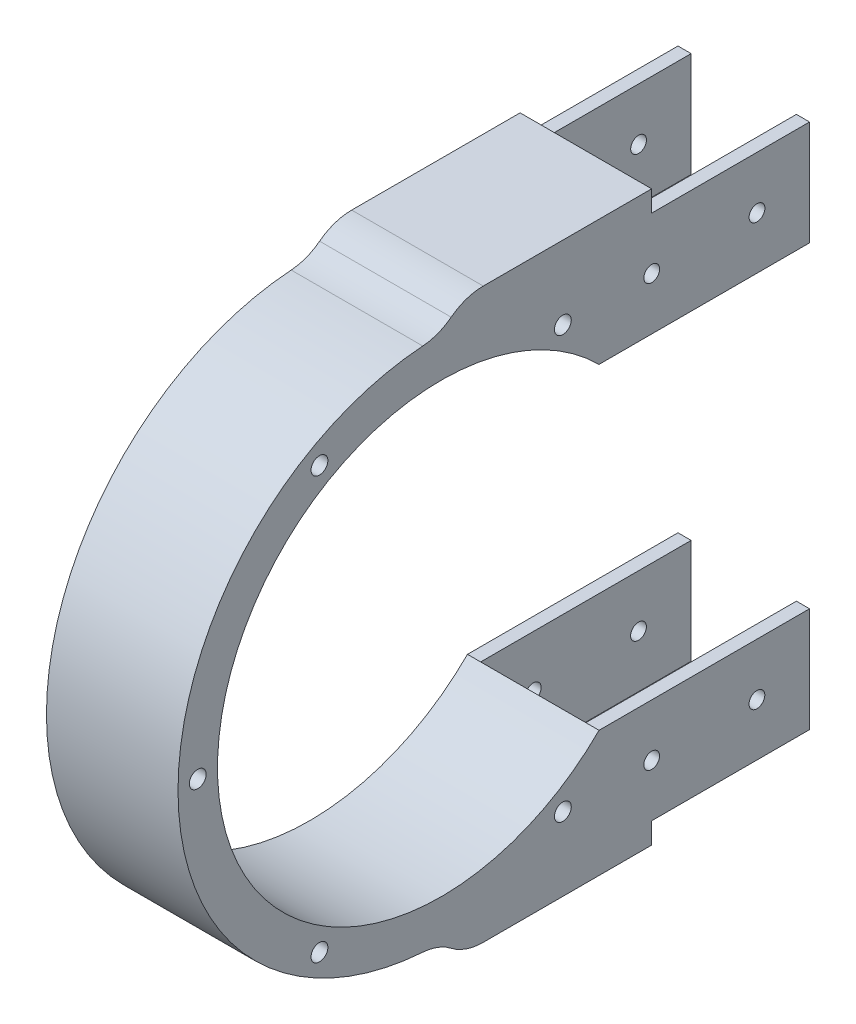
SolidWorks part; units mm, degrees
ref_plane "Front Plane" through (0, 0, 0) normal (0, 0, 1) x (1, 0, 0)
ref_plane "Top Plane" through (0, 0, 0) normal (0, 1, 0) x (1, 0, 0)
ref_plane "Right Plane" through (0, 0, 0) normal (1, 0, 0) x (0, 0, -1)
sketch "草图1" plane through (0, 0, 0) normal (1, 0, 0) x (0, 0, -1)
  line L0 (-50, 0) -> (-42.5, 0)
  line L1 (30, 30.104) -> (30, 50)
  line L2 (30, 50) -> (0, 50)
  line L3 (0, 50) -> (30, 50)
  line L4 (30, -30.104) -> (30, -50)
  line L5 (30, -50) -> (0, -50)
  arc A0 (0, 50) -> (0, -50) centre (0, 0) ccw
  arc A1 (30, 30.104) -> (30, -30.104) centre (0, 0) ccw
  circle A2 centre (-46.25, 0) radius 1.6
  circle A3 centre (-23.125, 40.0537) radius 1.6
  circle A4 centre (23.125, 40.0537) radius 1.6
  circle A6 centre (23.125, -40.0537) radius 1.6
  circle A7 centre (-23.125, -40.0537) radius 1.6
  circle A8 centre (46.25, 0) radius 1.6 [skipped]
  point P25 (0, 0)
  dimension "D1" = 100
  dimension "D2" = 85
  dimension "D3" = 3.2
  dimension "D4" = 6
extrude "凸台-拉伸1" add sketch "草图1" along normal blind 25 contours A2 L0 A1 L1 L2 A0 A4 A3 | A2 L0 A0 L5 L4 A1 A7 A6 region at (0, 2.5434, 46.25) region at (0, -0.9434, 43.575)
sketch "草图2" plane through (0, 0, -30) normal (0, 0, -1) x (-1, 0, 0)
  line L1 (-25, 50) -> (-22.5, 50)
  line L2 (-25, 50) -> (-25, 30.104)
  line L3 (-25, 30.104) -> (-22.5, 30.104)
  line L4 (-22.5, 50) -> (-22.5, 30.104)
  line L5 (-25, 30.104) -> (0, 30.104) construction
  line L6 (0, 0) -> (-70.7097, 0) construction
  line L7 (0, 50) -> (-2.5, 50)
  line L8 (0, 50) -> (0, 30.104)
  line L9 (0, 30.104) -> (-2.5, 30.104)
  line L10 (-2.5, 50) -> (-2.5, 30.104)
  line L11 (-2.5, -50) -> (-2.5, -30.104)
  line L12 (0, -30.104) -> (-2.5, -30.104)
  line L13 (0, -50) -> (0, -30.104)
  line L14 (0, -50) -> (-2.5, -50)
  line L15 (-22.5, -50) -> (-22.5, -30.104)
  line L16 (-25, -30.104) -> (-22.5, -30.104)
  line L17 (-25, -50) -> (-25, -30.104)
  line L18 (-25, -50) -> (-22.5, -50)
  dimension "D1" = 19.896
  dimension "D2" = 2.5
  dimension "D3" = 19.896
  dimension "D4" = 2.5
extrude "凸台-拉伸2" add sketch "草图2" along normal blind 40
sketch "草图3" plane through (25, 0, 0) normal (1, 0, 0) x (0, 0, -1)
  line L0 (70, -30.104) -> (70, -50) construction
  line L1 (0, 0.0089) -> (60, -0.0016) construction
  circle A0 centre (60, -40.052) radius 1.5
  circle A1 centre (40, -40.052) radius 1.5
  circle A2 centre (40.014, 40.0558) radius 1.5
  circle A3 centre (60.014, 40.0488) radius 1.5
  dimension "D1" = 3
  dimension "D2" = 3
  dimension "D3" = 10
  dimension "D4" = 20
extrude "切除-拉伸1" cut sketch "草图3" against normal through all
sketch "草图4" plane through (25, 0, 0) normal (1, 0, 0) x (0, 0, -1)
  line L0 (0, 0) -> (38.0446, 0) construction
  line L8 (40, 50) -> (40, 54)
  line L17 (0, -50) -> (40, -50)
  line L18 (0, -50) -> (0, -54)
  line L19 (0, -54) -> (40, -54)
  line L20 (40, -50) -> (40, -54)
  line L21 (0, 54) -> (40, 54)
  line L22 (0, 50) -> (0, 54)
  line L23 (0, 50) -> (40, 50)
  dimension "D1" = 4
  dimension "D2" = 40
extrude "凸台-拉伸3" add sketch "草图4" against normal blind 25
fillet "圆角4" radius 10 2 edges at (12.5, -54, 0) (12.5, 54, 0)
fillet "圆角5" radius 10 2 edges at (12.5, 50, 0) (12.5, -50, 0)
